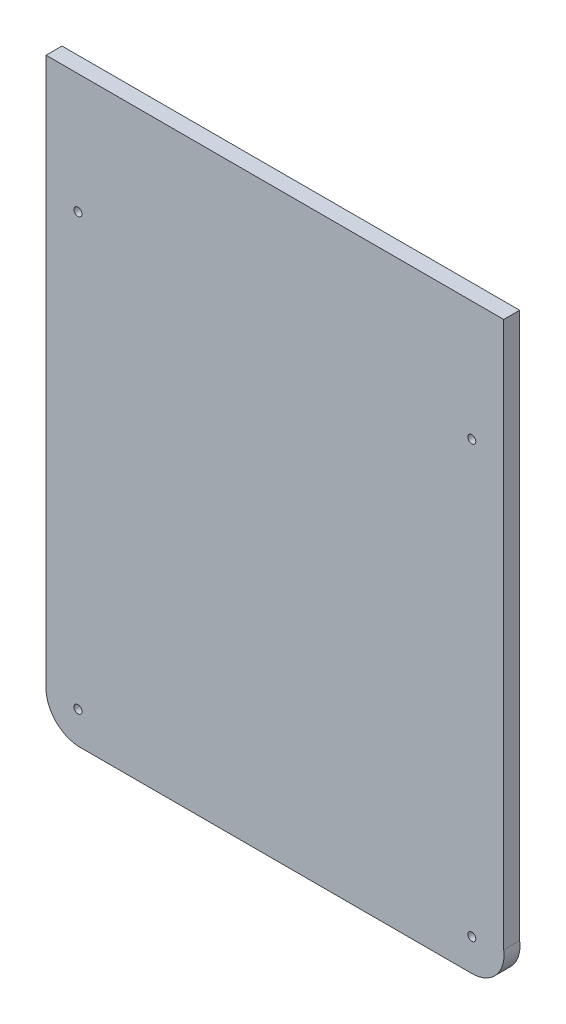
SolidWorks part; units mm, degrees
material "Beech"
ref_plane "Front Plane" through (0, 0, 0) normal (0, 0, 1) x (1, 0, 0)
ref_plane "Top Plane" through (0, 0, 0) normal (0, 1, 0) x (1, 0, 0)
ref_plane "Right Plane" through (0, 0, 0) normal (1, 0, 0) x (0, 0, -1)
sketch "Sketch1" plane through (0, 0, 0) normal (0, 0, 1) x (1, 0, 0)
  line L0 (-19.05, 903.0272) -> (-19.05, 155.124) construction
  line L1 (163.1, 903.0272) -> (163.1, 155.124) construction
  line L2 (-19.05, 920.1747) -> (163.1, 920.1747)
  line L5 (163.1, 683.9522) -> (163.1, 855.4022) construction
  line L6 (-6.35, 688.3997) -> (150.4, 688.3997)
  line L7 (163.1, 702.8437) -> (163.1, 920.1747)
  line L10 (-19.05, 920.1747) -> (-19.05, 701.0997)
  arc A2 (-19.05, 701.0997) -> (-6.35, 688.3997) centre (-5.3248, 702.1249) ccw
  arc A3 (150.4, 688.3997) -> (163.1, 702.8437) centre (150.5204, 701.0991) ccw
  point P2 (-19.05, 920.1747)
  point P5 (0, 0)
  point P11 (-19.05, 701.0997)
  point P14 (-6.35, 688.3997)
  point P15 (150.4, 688.3997)
  point P16 (0, 0)
  point P17 (0, 0)
  point P18 (163.1, 702.8437)
extrude "Boss-Extrude1" add sketch "Sketch1" along normal blind 6.35
hole_wizard "Hole1" positions "Sketch2" profile "Sketch3" legacy
sketch "Sketch2" plane through (72.025, -420.4895, 19.05) normal (0, 0, 1) x (1, 0, 0)
  point P0 (-78.375, 1293.0392)
  point P3 (-78.375, 1121.5892)
  point P6 (78.375, 1121.5892)
  point P9 (78.375, 1293.0392)
  point P12 (-764.0155, 1530.0782)
sketch "Sketch3" plane through (-6.35, 872.5497, 19.05) normal (1, 0, 0) x (0, -1, 0)
  line L0 (0, 0) -> (0, 32.7039)
  line L1 (0, 32.7039) -> (1.5875, 31.75)
  line L2 (1.5875, 31.75) -> (1.5875, 4.0177)
  line L3 (1.5875, 4.0177) -> (5.08, 0)
  line L4 (5.08, 0) -> (0, 0)
  line L5 (0, -14.3089) -> (0, 102.4216) construction
  line L6 (0, 32.7039) -> (-1.5875, 31.75) construction
  line L7 (-1.5875, 4.0177) -> (-5.08, 0) construction
  dimension "Diameter" = 3.175
  dimension "Depth" = 31.75
  dimension "C-Sink Diameter" = 10.16
  dimension "C-Sink Angle" = 82
  dimension "Drill Angle" = 118
